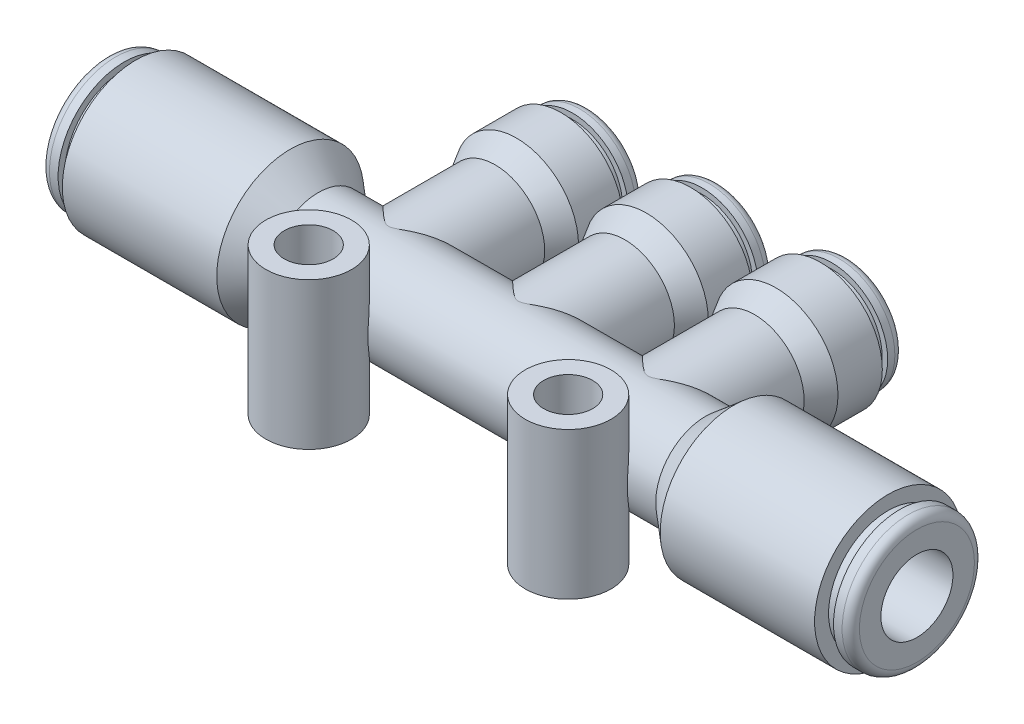
SolidWorks part; units mm, degrees
ref_plane "Front Plane" through (0, 0, 0) normal (0, 0, 1) x (1, 0, 0)
ref_plane "Top Plane" through (0, 0, 0) normal (0, 1, 0) x (1, 0, 0)
ref_plane "Right Plane" through (0, 0, 0) normal (1, 0, 0) x (0, 0, -1)
sketch "Sketch8" plane through (0, 0, 0) normal (1, 0, 0) x (0, 0, -1)
  line L0 (16.764, 4.9149) -> (17.399, 4.9149)
  line L1 (11.8401, 5.461) -> (15.748, 5.461)
  line L2 (0, 4.3688) -> (0, 1.9844)
  line L3 (0, 1.9844) -> (17.78, 1.9844)
  line L4 (18.161, 4.1529) -> (18.161, 2.3654)
  line L5 (0, 5.461) -> (0, -12.7) construction
  line L6 (15.748, 5.461) -> (15.748, 4.4234)
  line L7 (15.748, 4.4234) -> (16.764, 4.4234)
  line L8 (16.764, 4.9149) -> (16.764, 4.4234)
  line L9 (-6.477, -12.7) -> (6.477, -12.7) construction
  line L10 (0, 0) -> (18.161, 0) construction
  line L12 (17.78, 1.9844) -> (18.161, 2.3654)
  line L13 (0, 0) -> (0, 10.8701) construction
  line L14 (0, 4.3688) -> (9.9483, 4.3688)
  line L15 (9.9483, 4.3688) -> (11.8401, 5.461)
  arc A0 (17.399, 4.9149) -> (18.161, 4.1529) centre (17.399, 4.1529) cw
  point P1 (18.161, 1.9844)
  point P20 (18.161, 4.9149)
  dimension "D4" = 0.762
  dimension "tube od" = 3.9688
  dimension "D1" = 1.397
  dimension "D2" = 1.016
  dimension "D3" = 8.8468
  dimension "D6" = 9.8298
  dimension "D9" = 30
  dimension "D10" = 8.7376
  dimension "D5" = 8.2127
  dimension "D8" = 12.954
revolve "Revolve1" add sketch "Sketch8" angle 360 about L10
sketch "Sketch10" plane through (0, 0, 0) normal (0, 0, 1) x (1, 0, 0)
  line L0 (0, 0) -> (8.5418, 0) construction
sketch "Sketch9" plane through (0, 0, 0) normal (0, 0, 1) x (1, 0, 0)
  circle A0 centre (0, 0) radius 1.9844 construction
  circle A1 centre (0, 0) radius 1.9844
  circle A2 centre (0, 0) radius 1.2224
  dimension "D1" = 0.762
extrude "Extrude1" add sketch "Sketch9" against normal blind 4.3688
pattern_linear "LPattern1" count 2 spacing 11.43 along (-1, 0, 0) count 2 spacing 11.43 along (1, 0, 0) of bodies 123 127
sketch "Sketch14" plane through (0, 0, 0) normal (0, 1, 0) x (1, 0, 0)
  line L0 (35.687, 0) -> (-35.687, 0) construction
  line L1 (35.687, -3.175) -> (18.3388, -3.175)
  line L2 (35.687, -3.175) -> (35.687, -5.0673)
  line L3 (34.925, -5.8293) -> (34.163, -5.8293)
  line L4 (34.163, -5.8293) -> (34.163, -5.2464)
  line L5 (34.163, -5.2464) -> (33.147, -5.2464)
  line L6 (33.147, -5.2464) -> (33.147, -6.477)
  line L7 (33.147, -6.477) -> (19.5389, -6.477)
  line L8 (11.43, -6.477) -> (19.5389, -6.477) construction
  line L9 (17.0688, -4.4044) -> (0, -4.4044)
  line L10 (18.3388, -3.175) -> (18.3388, -2.413)
  line L11 (18.3388, -2.413) -> (0, -2.413)
  line L12 (0, -2.413) -> (0, -4.4044)
  line L13 (0, 0) -> (0, -6.477) construction
  line L14 (-11.43, -6.477) -> (11.43, -6.477) construction
  line L15 (17.0688, -4.4044) -> (19.5389, -6.477)
  line L16 (15.7988, 0) -> (15.7988, 9.9483) construction
  arc A0 (35.687, -5.0673) -> (34.925, -5.8293) centre (34.925, -5.0673) cw
  dimension "D8" = 0.762
  dimension "L" = 71.374
  dimension "D2" = 0.762
  dimension "D4" = 11.6586
  dimension "D5" = 10.4927
  dimension "D6" = 1.524
  dimension "D7" = 1.016
  dimension "D9" = 8.8087
  dimension "D1" = 40
  dimension "D10" = 1.27
  dimension "D3" = 1.27
revolve "Revolve3" add sketch "Sketch14" angle 360 about L0
sketch "Sketch16" plane through (0, 0, -4.3688) normal (0, 0, 1) x (-1, 0, 0)
  line L0 (13.4144, 0) -> (9.4456, 0) construction
  circle A1 centre (11.43, 0) radius 1.9844 construction
  circle A2 centre (0, 0) radius 1.9844 construction
  circle A6 centre (-11.43, 0) radius 1.9844 construction
  circle A7 centre (11.43, 0) radius 1.9844
  circle A8 centre (0, 0) radius 1.9844
  circle A9 centre (-11.43, 0) radius 1.9844
  point P9 (11.43, 0)
  point P10 (0, 0)
  point P11 (-11.43, 0)
sketch "Sketch17" plane through (0, 0, 0) normal (0, 0, 1) x (1, 0, 0)
  circle A1 centre (0, 0) radius 1.2224 construction
  circle A2 centre (-11.43, 0) radius 1.2224 construction
  circle A3 centre (0, 0) radius 1.2224
  circle A6 centre (-11.43, 0) radius 1.2224
  circle A7 centre (11.43, 0) radius 1.2224 construction
  circle A8 centre (11.43, 0) radius 1.2224
mirror "Mirror3" about plane through (0, 0, 0) normal (1, 0, 0) of bodies 132 133
combine bodies "Combine2" operation type add bodies to combine 134 132 131 130 129 123
extrude "Cut-Extrude4" cut sketch "Sketch16" against normal through all
extrude "Cut-Extrude5" cut sketch "Sketch17" against normal through all
sketch "Sketch15" plane through (-18.3388, 0, 0) normal (-1, 0, 0) x (0, 0, 1)
  circle A0 centre (0, 0) radius 2.413 construction
  circle A1 centre (0, 0) radius 2.413
extrude "Cut-Extrude3" cut sketch "Sketch15" against normal through all
sketch "Sketch18" plane through (0, 0, 0) normal (0, 1, 0) x (1, 0, 0)
  line L0 (0, 0) -> (0, -6.477) construction
  line L1 (-11.43, -6.477) -> (11.43, -6.477) construction
  line L2 (35.687, 0) -> (-35.687, 0) construction
  line L3 (-13.4144, 17.78) -> (-9.4456, 17.78) construction
  line L4 (13.7954, 18.161) -> (9.0646, 18.161) construction
  line L5 (2.3654, 18.161) -> (-2.3654, 18.161) construction
  line L6 (-9.0646, 18.161) -> (-13.7954, 18.161) construction
  circle A0 centre (-11.43, -6.477) radius 2.159
  circle A1 centre (-11.43, -6.477) radius 3.7783
  circle A2 centre (11.43, -6.477) radius 3.7782
  circle A3 centre (11.43, -6.477) radius 2.159
  point P13 (-11.43, 18.161)
  point P14 (0, 18.161)
  point P15 (11.43, 18.161)
  dimension "D2" = 7.5565
  dimension "D1" = 22.86
extrude "Extrude2" add sketch "Sketch18" along normal mid plane 12.954
sketch "Sketch19" plane through (0, 0, 0) normal (0, 1, 0) x (1, 0, 0)
  line L0 (9.271, -3.3764) -> (9.271, -3.175)
  line L1 (9.271, -3.175) -> (13.589, -3.175)
  line L2 (13.589, -3.175) -> (13.589, -3.3764)
  line L3 (-13.589, -3.3764) -> (-13.589, -3.175)
  line L4 (-13.589, -3.175) -> (-9.271, -3.175)
  line L5 (-9.271, -3.175) -> (-9.271, -3.3764)
  line L6 (0, 0) -> (35.687, 0) construction
  circle A0 centre (-11.43, -6.477) radius 3.7783 construction
  arc A1 (-9.271, -3.3764) -> (-13.589, -3.3764) centre (-11.43, -6.477) ccw
  circle A2 centre (11.43, -6.477) radius 3.7782 construction
  arc A3 (13.589, -3.3764) -> (9.271, -3.3764) centre (11.43, -6.477) ccw
  circle A4 centre (11.43, -6.477) radius 2.159 construction
  circle A6 centre (-11.43, -6.477) radius 2.159 construction
  dimension "D1" = 6.35
extrude "Extrude3" [suppressed] add sketch "Sketch19" along normal mid plane 6.477
extrude "Cut-Extrude6" cut sketch "Sketch18<2>" against normal through all and the other way through all contours A0 | A3
sketch "Sketch18<2>" plane through (0, 0, 0) normal (0, 1, 0) x (1, 0, 0) same geometry as "Sketch18"
equation "\"D6@Sketch8\" = \"G@Sketch8\"*.9"
equation "\"D3@Sketch8\" = \"D6@Sketch8\"*.9"
equation "\"D10@Sketch8\" = \"G@Sketch8\"*.8"
equation "\"D1@Extrude1\" = \"D10@Sketch8\"/2"
equation "\"D4@LPattern1\" = \"N@LPattern1\""
equation "\"D4@Sketch14\" = \"G@Sketch14\"*.9"
equation "\"D5@Sketch14\" = \"D4@Sketch14\"*.9"
equation "\"D9@Sketch14\" = \"G@Sketch14\"*.68"
equation "\"D2@Sketch18\" = \"T@Sketch18\"*1.75"
equation "\"D1@Sketch18\" = \"M@Sketch14\""
equation "\"D1@Extrude2\" = \"G@Sketch14\""
equation "\"D1@Sketch19\" = \"tube od 2@Sketch14\""
equation "\"D1@Extrude3\" = \"D1@Extrude2\"/2"
equation "\"D8@Sketch8\" = \"G@Sketch14\""
equation "\"D5@Sketch8\" = \"H@Sketch8\"/3"
